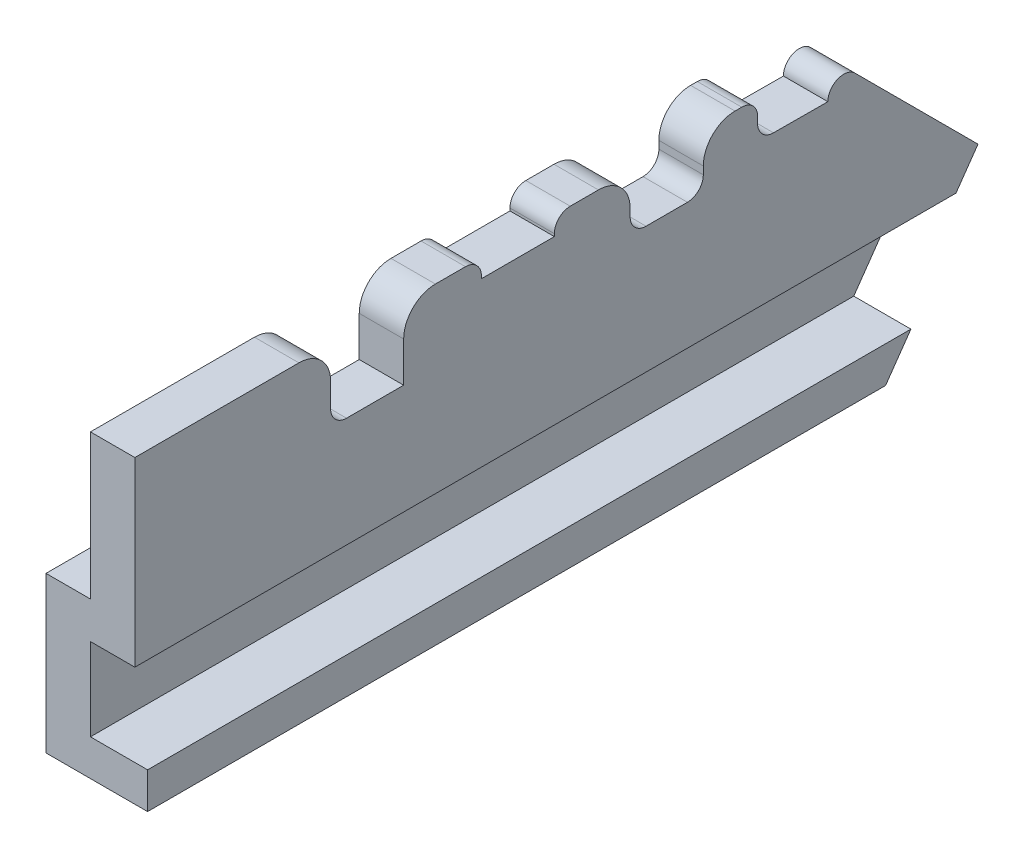
SolidWorks part; units mm, degrees
note: The reader was unsure of these and kept them because the rebuilt part matched: shared geometry of "3DSketch1<3>", "3DSketch1<4>", "3DSketch1<5>".
ref_plane "Front Plane" through (0, 0, 0) normal (0, 0, 1) x (1, 0, 0)
ref_plane "Top Plane" through (0, 0, 0) normal (0, 1, 0) x (1, 0, 0)
ref_plane "Right Plane" through (0, 0, 0) normal (1, 0, 0) x (0, 0, -1)
sketch "Sketch1" plane through (0, 0, 0) normal (0, 0, 1) x (1, 0, 0)
  line L0 (0, 3.8362) -> (0, -3.8362) construction
  line L1 (0, 0) -> (0, 2.28)
  line L2 (0, 2.28) -> (0.7, 2.28)
  line L3 (0.7, 2.28) -> (0.7, -0.58)
  line L4 (0.7, -0.58) -> (0, -0.58)
  line L5 (0, -0.58) -> (0, -1.88)
  line L6 (0.9, -1.88) -> (0, -1.88)
  line L7 (0.9, -1.88) -> (0.9, -2.45)
  line L8 (0.9, -2.45) -> (-0.7, -2.45)
  line L9 (-0.7, -2.45) -> (-0.7, 0)
  line L10 (-0.7, 0) -> (0, 0)
  dimension "D1" = 0.7
  dimension "D2" = 2.86
  dimension "D3" = 1.3
  dimension "D4" = 2.45
  dimension "D5" = 4.73
  dimension "D6" = 1.6
  dimension "D7" = 0.7
extrude "Boss-Extrude1" add sketch "Sketch1" along normal blind 13.28
sketch "Sketch2" plane through (0, 0, 0) normal (1, 0, 0) x (0, 0, -1)
  line L0 (-6.64, 2.28) -> (-6.64, -2.45) construction
  line L1 (-13.28, 2.28) -> (0, 2.28) construction
  line L2 (-13.28, -2.45) -> (0, -2.45) construction
  line L3 (-6.64, -0.085) -> (-13.7893, -0.085) construction
  line L4 (-13.28, -0.085) -> (-10.615, 2.58) construction
  line L5 (-13.28, -0.58) -> (-13.28, 2.28) construction
  line L6 (-10.615, 2.58) -> (-14.08, 2.58) construction
  line L7 (-14.08, 2.58) -> (-14.08, -0.085) construction
  line L8 (-13.28, -0.085) -> (-11.4139, -2.75) construction
  line L9 (-11.4139, -2.75) -> (-14.08, -2.75) construction
  line L10 (-14.08, -2.75) -> (-14.08, -0.085) construction
  line L11 (0.8, -2.75) -> (0.8, -0.085)
  line L12 (-1.8661, -2.75) -> (0.8, -2.75)
  line L13 (0, -0.085) -> (-1.8661, -2.75)
  line L14 (0.8, 2.58) -> (0.8, -0.085)
  line L15 (-2.665, 2.58) -> (0.8, 2.58)
  line L16 (0, -0.085) -> (-2.665, 2.58)
  dimension "D1" = 45
  dimension "D2" = 55
  dimension "D3" = 0.3
  dimension "D4" = 0.3
  dimension "D5" = 0.8
extrude "Cut-Extrude1" cut sketch "Sketch2" against normal through all both and the other way through all
sketch3d "3DSketch1"
  line L0 (0, 2.28, 13.28) -> (0, 2.28, 2.365) construction
  line L1 (0.0493, 2.28, 13.28) -> (0.0493, 2.28, 3.48) construction
  line L2 (0, 2.28, 10.1964) -> (0, 2.28, 9.0464)
  line L3 (0, 2.28, 10.1964) -> (0.7, 2.28, 10.1964)
  line L4 (0.7, 2.28, 10.1964) -> (0.7, 2.28, 9.0464)
  line L5 (0, 2.28, 9.0464) -> (0.7, 2.28, 9.0464)
  line L6 (0.2936, 2.28, 13.28) -> (0.2936, 2.28, 10.25) construction
  line L7 (0.7, 2.28, 13.28) -> (0, 2.28, 13.28) construction
  line L8 (0.5055, 2.28, 13.28) -> (0.5055, 2.28, 7.81) construction
  line L9 (0.1317, 2.28, 13.28) -> (0.1317, 2.28, 5.48) construction
  line L10 (0.7, 2.28, 13.28) -> (0.7, 2.28, 2.365) construction
  line L12 (0.7, 2.28, 7.8225) -> (0.7, 2.28, 6.6725)
  line L13 (0.7, 2.28, 7.8225) -> (0, 2.28, 7.8225)
  line L14 (0, 2.28, 7.8225) -> (0, 2.28, 6.6725)
  line L15 (0.7, 2.28, 6.6725) -> (0, 2.28, 6.6725)
  line L16 (0, 2.28, 5.4786) -> (0, 2.28, 4.3268)
  line L17 (0, 2.28, 5.4786) -> (0.7, 2.28, 5.4786)
  line L18 (0.7, 2.28, 5.4786) -> (0.7, 2.28, 4.3268)
  line L19 (0, 2.28, 4.3268) -> (0.7, 2.28, 4.3268)
  line L20 (0, 2.28, 3.4712) -> (0, 2.28, 2.365)
  line L21 (0, 2.28, 3.4712) -> (0.7, 2.28, 3.4712)
  line L22 (0.7, 2.28, 3.4712) -> (0.7, 2.28, 2.365)
  line L23 (0, 2.28, 2.365) -> (0.7, 2.28, 2.365)
extrude "Cut-Extrude5" cut sketch "3DSketch1" along direction (0, -1, 0) on the side against the normal blind 0.29 contours L13 L14 L15 L12
extrude "Cut-Extrude6" cut sketch "3DSketch1<3>" along direction (0, -1, 0) on the side against the normal blind 1.13 contours L2 L5 L4 L3
sketch3d "3DSketch1<3>" same geometry as "3DSketch1"
extrude "Cut-Extrude7" cut sketch "3DSketch1<4>" along direction (0, -1, 0) on the side against the normal blind 0.87 contours L19 L18 L17 L16
sketch3d "3DSketch1<4>" same geometry as "3DSketch1"
extrude "Cut-Extrude8" cut sketch "3DSketch1<5>" along direction (0, -1, 0) on the side of the normal blind 0.6 contours L20 L23 L22 L21
sketch3d "3DSketch1<5>" same geometry as "3DSketch1"
fillet "Fillet7" radius 0.5 5 edges
fillet "Fillet8" radius 0.5 3 edges
fillet "Fillet13" radius 0.25 5 edges
fillet "Fillet14" radius 0.25 3 edges
fillet "Fillet15" radius 0.5 3 edges
fillet "Fillet16" radius 0.5 5 edges
fillet "Fillet18" radius 0.25 3 edges
fillet "Fillet19" radius 0.25 4 edges
fillet "Fillet20" radius 0.25 3 edges
fillet "Fillet21" radius 0.25 1 edges
fillet "Fillet23" radius 0.25 3 edges
fillet "Fillet25" radius 0.25 3 edges
